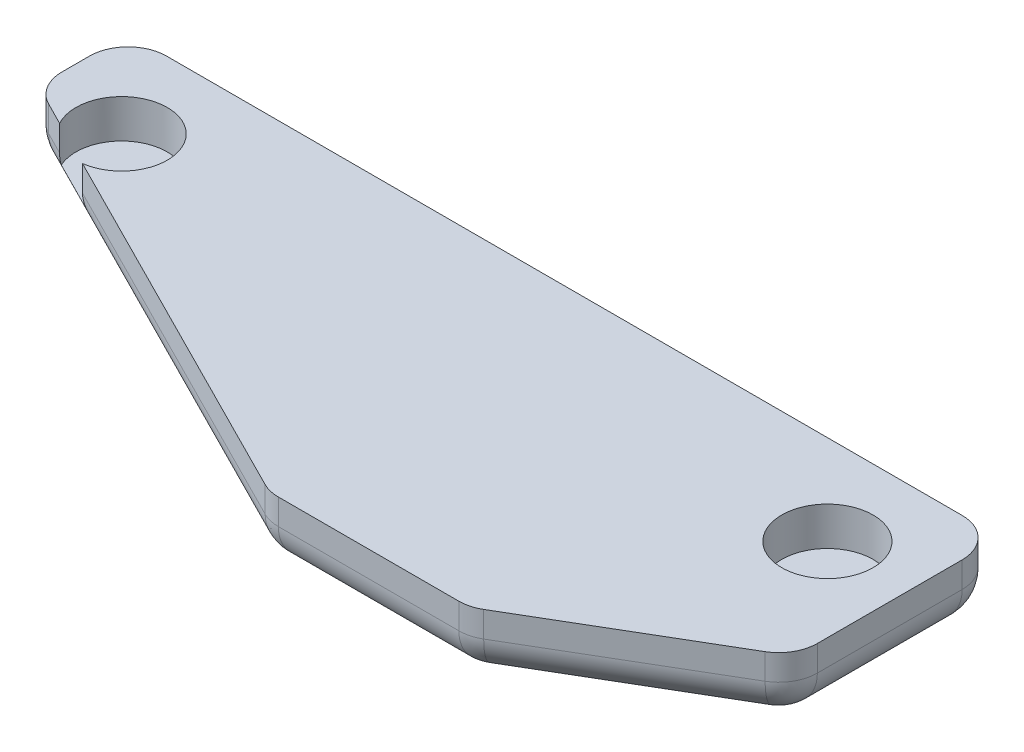
SolidWorks part; units mm, degrees
ref_plane "Front Plane" through (0, 0, 0) normal (0, 0, 1) x (1, 0, 0)
ref_plane "Top Plane" through (0, 0, 0) normal (0, 1, 0) x (1, 0, 0)
ref_plane "Right Plane" through (0, 0, 0) normal (1, 0, 0) x (0, 0, -1)
sketch "Sketch2" plane through (0, 0, 0) normal (0, 1, 0) x (1, 0, 0)
  line L0 (-21.2162, 11.7419) -> (-21.2162, 8.2419)
  line L1 (-21.2162, 8.2419) -> (-3.0162, -0.9581)
  line L2 (-3.0162, -0.9581) -> (4.7838, -0.9581)
  line L3 (4.7838, -0.9581) -> (12.7838, 3.7419)
  line L4 (12.7838, 3.7419) -> (12.7838, 11.7419)
  line L7 (-21.2162, 11.7419) -> (12.7838, 11.7419)
  dimension "D1" = 34
  dimension "D2" = 12.7
  dimension "D3" = 8
  dimension "D4" = 8
  dimension "D5" = 3.5
  dimension "D6" = 7.8
extrude "Boss-Extrude1" add sketch "Sketch2" along normal blind 2.5
sketch "Sketch4" plane through (0, 2.5, 0) normal (0, 1, 0) x (1, 0, 0)
  line L0 (-17.9662, 11.241) -> (-17.9662, -1.2869) construction
  line L1 (-21.2162, 8.2419) -> (12.7838, 8.2419) construction
  line L2 (-21.2162, 11.7419) -> (-21.2162, 8.2419) construction
  line L3 (12.7838, 11.7419) -> (-21.2162, 11.7419) construction
  line L4 (-4.2162, 11.7419) -> (-4.2162, -0.9581) construction
  line L5 (-3.0162, -0.9581) -> (4.7838, -0.9581) construction
  line L6 (9.5338, 11.241) -> (9.5338, -1.2869) construction
  circle A0 centre (-17.9662, 8.2419) radius 1.78
  circle A1 centre (9.5338, 8.2419) radius 1.78
  point P15 (-4.2162, 8.2419)
  dimension "D1" = 3.25
  dimension "D2" = 3.5
extrude "Cut-Extrude1" cut sketch "Sketch4" against normal blind 1.5
fillet "Fillet1" radius 1.5 12 edges at (4.7838, 1.25, 0.9581) (-3.0162, 1.25, 0.9581) (-21.2162, 0, -9.9919) (-12.1162, 0, -3.6419) (0.8838, 0, 0.9581) (8.7838, 0, -1.3919) (12.7838, 1.25, -3.7419) (12.7838, 0, -7.7419) (-4.2162, 0, -11.7419) (12.7838, 1.25, -11.7419) (-21.2162, 1.25, -8.2419) (-21.2162, 1.25, -11.7419)
